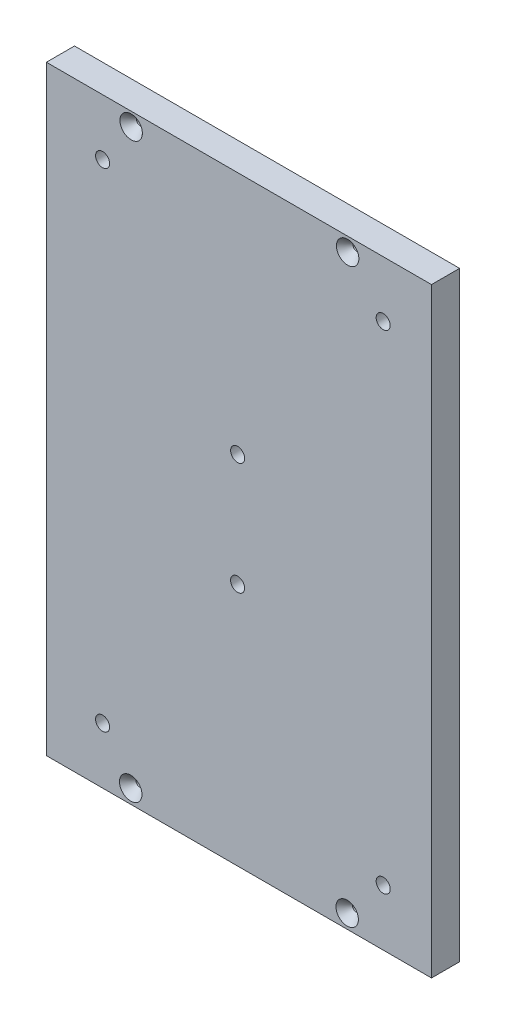
SolidWorks part; units mm, degrees
material "Beech"
ref_plane "Front Plane" through (0, 0, 0) normal (0, 0, 1) x (1, 0, 0)
ref_plane "Top Plane" through (0, 0, 0) normal (0, 1, 0) x (1, 0, 0)
ref_plane "Right Plane" through (0, 0, 0) normal (1, 0, 0) x (0, 0, -1)
sketch "Sketch1" plane through (0, 0, 0) normal (0, 0, 1) x (1, 0, 0)
  line L2 (125.2425, 0) -> (299.2638, 0)
  line L3 (125.2425, 0) -> (125.2425, 271.3655)
  line L4 (125.2425, 135.6828) -> (299.2638, 135.6828) construction
  line L5 (299.2638, 0) -> (299.2638, 271.3655)
  line L8 (125.2425, 271.3655) -> (299.2638, 271.3655)
  line L9 (299.2638, 0) -> (299.2638, 271.3655) construction
  point P15 (299.2638, 135.6828)
  point P16 (299.2638, 135.6828)
extrude "Boss-Extrude1" add sketch "Sketch1" along normal blind 12.7
hole_wizard "1/4 (0.25) Diameter Hole1" positions "Sketch2" profile "Sketch3" hole size "1/4" standard "ANSI Inch" end condition through all
sketch "Sketch2" plane through (0, 0, 0) normal (0, 0, -1) x (-1, 0, 0)
  point P0 (-277.4266, 245.9655)
  point P3 (-211.6533, 161.0828)
  point P6 (-150.6425, 245.9655)
  point P9 (-211.6533, 110.2828)
  point P12 (-277.4266, 25.4)
  point P15 (-150.6425, 25.4)
sketch "Sketch3" plane through (277.4266, 245.9655, 0) normal (1, 0, 0) x (0, 1, 0)
  line L0 (0, 0) -> (0, 12.7)
  line L1 (0, 12.7) -> (3.175, 12.7)
  line L2 (3.175, 12.7) -> (3.175, 0)
  line L5 (3.175, 0) -> (0, 0)
  line L11 (0, -6.35) -> (0, 107.95) construction
  dimension "Thru Hole Dia." = 6.35
  dimension "Thru Hole Depth" = 12.7
hole_wizard "Hole1" positions "Sketch4" profile "Sketch5" legacy
sketch "Sketch4" plane through (-499.6721, 135.8167, 12.7) normal (0, 0, 1) x (0, -1, 0)
  line L0 (129.4667, 798.9359) -> (129.4667, 624.9146) construction
  line L5 (0.134, 798.9359) -> (0, 625.1618) construction
  point P10 (129.4667, 663.0146)
  point P12 (129.4667, 760.8359)
  point P20 (-129.4082, 663.2142)
  point P21 (-129.2574, 761.0354)
sketch "Sketch5" plane through (261.3633, 265.0741, 12.7) normal (1, 0, 0) x (0, -1, 0)
  line L0 (0, 0) -> (0, 32.7039)
  line L1 (0, 32.7039) -> (1.5875, 31.75)
  line L2 (1.5875, 31.75) -> (1.5875, 4.0177)
  line L3 (1.5875, 4.0177) -> (5.08, 0)
  line L4 (5.08, 0) -> (0, 0)
  line L5 (0, -14.3089) -> (0, 102.4216) construction
  line L6 (0, 32.7039) -> (-1.5875, 31.75) construction
  line L7 (-1.5875, 4.0177) -> (-5.08, 0) construction
  dimension "Diameter" = 3.175
  dimension "Depth" = 31.75
  dimension "C-Sink Diameter" = 10.16
  dimension "C-Sink Angle" = 82
  dimension "Drill Angle" = 118
